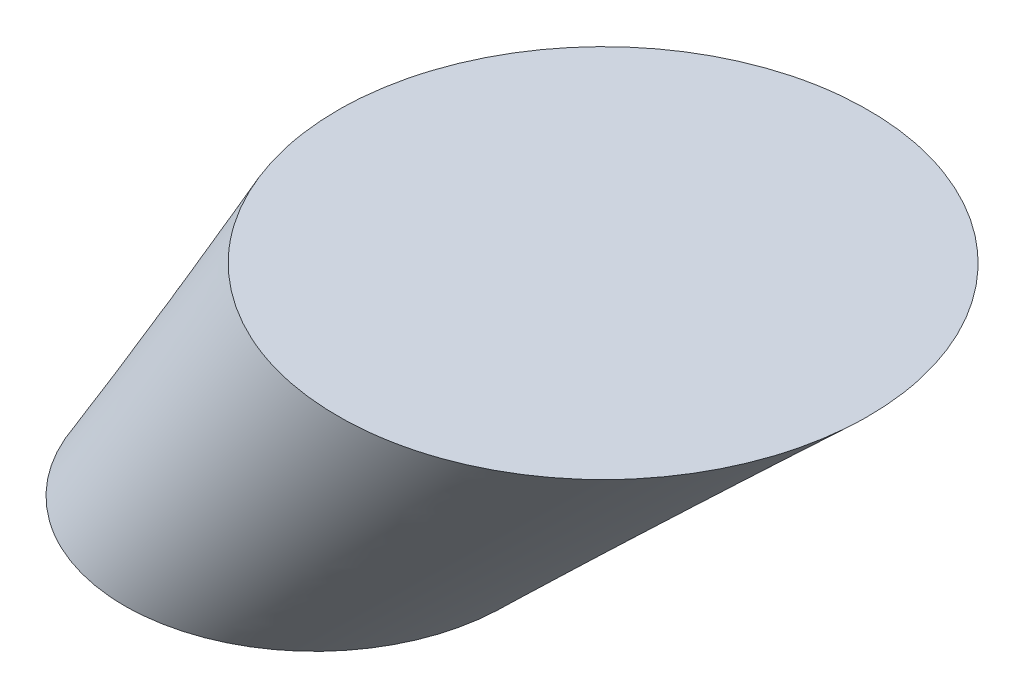
SolidWorks part; units mm, degrees
ref_plane "Front Plane" through (0, 0, 0) normal (0, 0, 1) x (1, 0, 0)
ref_plane "Top Plane" through (0, 0, 0) normal (0, 1, 0) x (1, 0, 0)
ref_plane "Right Plane" through (0, 0, 0) normal (1, 0, 0) x (0, 0, -1)
sketch "Sketch1" plane through (0, 0, 0) normal (0, 1, 0) x (1, 0, 0)
  line L0 (0, 0) -> (-47.9811, 0) construction
  circle A0 centre (0, 0) radius 23
  dimension "D1" = 46
ref_plane "Plane1" through (0, -30, 0) normal (0, -1, 0) x (-1, 0, 0)
sketch "Sketch9" plane through (0, -30, 0) normal (0, -1, 0) x (-1, 0, 0)
  circle A0 centre (25, 0) radius 16.5
  dimension "D1" = 33
  dimension "D2" = 25
loft "Loft1" add profiles "Sketch9", "Sketch1" connector at (-20.6661, -30, -15.9207) connector at (1.0526, 0, -22.9759)
sketch "Sketch13" plane through (0, 0, 0) normal (0, 1, 0) x (1, 0, 0)
  circle A0 centre (0, 0) radius 20
  dimension "D1" = 40
sketch "Sketch14" plane through (0, -30, 0) normal (0, -1, 0) x (1, 0, 0)
  circle A0 centre (-25, 0) radius 13.5
  dimension "D1" = 27
ref_plane "Plane2" through (0, -12.9, 0) normal (0, -1, 0) x (-1, 0, 0)
sketch "Sketch20" plane through (0, -12.9, 0) normal (0, -1, 0) x (-1, 0, 0)
  spline S0 degree 3 poles (9.1174, 20.0448) (7.4555, 19.8395) (6.5785, 19.6788) (4.7436, 19.1985) (3.7855, 18.8786) (1.817, 18.0307) (0.8064, 17.5024) (-1.2126, 16.1896) (-2.2211, 15.4047) (-4.1512, 13.5465) (-5.0724, 12.4726) (-6.7172, 10.0405) (-7.4398, 8.6818) (-8.5709, 5.7398) (-8.9781, 4.1568) (-9.3918, 0.8854) (-9.3974, -0.8017) (-8.9869, -4.1254) (-8.5708, -5.7604) (-7.3734, -8.8327) (-6.5932, -10.2691) (-4.7802, -12.8474) (-3.7487, -13.9894) (-1.5614, -15.9481) (-0.4066, -16.7655) (1.9177, -18.0981) (3.0868, -18.6141) (5.3646, -19.396) (6.4734, -19.6626) (8.589, -20.0059) (9.5962, -20.083) (11.4929, -20.1024) (12.3826, -20.0448) (14.0445, -19.8395) (14.9215, -19.6788) (16.7564, -19.1985) (17.7145, -18.8786) (19.683, -18.0307) (20.6936, -17.5024) (22.7126, -16.1896) (23.7211, -15.4047) (25.6512, -13.5465) (26.5724, -12.4726) (28.2172, -10.0405) (28.9398, -8.6818) (30.0709, -5.7398) (30.4781, -4.1568) (30.8918, -0.8854) (30.8974, 0.8017) (30.4869, 4.1254) (30.0708, 5.7604) (28.8734, 8.8327) (28.0932, 10.2691) (26.2802, 12.8474) (25.2487, 13.9894) (23.0614, 15.9481) (21.9066, 16.7655) (19.5823, 18.0981) (18.4132, 18.6141) (16.1354, 19.396) (15.0266, 19.6626) (12.911, 20.0059) (11.9038, 20.083) (10.0071, 20.1024) (9.1174, 20.0448) (7.4555, 19.8395) (6.5785, 19.6788) knots -0.03125 -0.03125 0 0 0.03125 0.03125 0.0625 0.0625 0.09375 0.09375 0.125 0.125 0.15625 0.15625 0.1875 0.1875 0.21875 0.21875 0.25 0.25 0.28125 0.28125 0.3125 0.3125 0.34375 0.34375 0.375 0.375 0.40625 0.40625 0.4375 0.4375 0.46875 0.46875 0.5 0.5 0.53125 0.53125 0.5625 0.5625 0.59375 0.59375 0.625 0.625 0.65625 0.65625 0.6875 0.6875 0.71875 0.71875 0.75 0.75 0.78125 0.78125 0.8125 0.8125 0.84375 0.84375 0.875 0.875 0.90625 0.90625 0.9375 0.9375 0.96875 0.96875 1 1 1.03125 1.03125 1.0625 only from (8.2865, 19.9421) to (8.2865, 19.9421)
  spline S1 degree 3 poles (9.1174, 20.0448) (7.4555, 19.8395) (6.5785, 19.6788) (4.7436, 19.1985) (3.7855, 18.8786) (1.817, 18.0307) (0.8064, 17.5024) (-1.2126, 16.1896) (-2.2211, 15.4047) (-4.1512, 13.5465) (-5.0724, 12.4726) (-6.7172, 10.0405) (-7.4398, 8.6818) (-8.5709, 5.7398) (-8.9781, 4.1568) (-9.3918, 0.8854) (-9.3974, -0.8017) (-8.9869, -4.1254) (-8.5708, -5.7604) (-7.3734, -8.8327) (-6.5932, -10.2691) (-4.7802, -12.8474) (-3.7487, -13.9894) (-1.5614, -15.9481) (-0.4066, -16.7655) (1.9177, -18.0981) (3.0868, -18.6141) (5.3646, -19.396) (6.4734, -19.6626) (8.589, -20.0059) (9.5962, -20.083) (11.4929, -20.1024) (12.3826, -20.0448) (14.0445, -19.8395) (14.9215, -19.6788) (16.7564, -19.1985) (17.7145, -18.8786) (19.683, -18.0307) (20.6936, -17.5024) (22.7126, -16.1896) (23.7211, -15.4047) (25.6512, -13.5465) (26.5724, -12.4726) (28.2172, -10.0405) (28.9398, -8.6818) (30.0709, -5.7398) (30.4781, -4.1568) (30.8918, -0.8854) (30.8974, 0.8017) (30.4869, 4.1254) (30.0708, 5.7604) (28.8734, 8.8327) (28.0932, 10.2691) (26.2802, 12.8474) (25.2487, 13.9894) (23.0614, 15.9481) (21.9066, 16.7655) (19.5823, 18.0981) (18.4132, 18.6141) (16.1354, 19.396) (15.0266, 19.6626) (12.911, 20.0059) (11.9038, 20.083) (10.0071, 20.1024) (9.1174, 20.0448) (7.4555, 19.8395) (6.5785, 19.6788) knots -0.03125 -0.03125 0 0 0.03125 0.03125 0.0625 0.0625 0.09375 0.09375 0.125 0.125 0.15625 0.15625 0.1875 0.1875 0.21875 0.21875 0.25 0.25 0.28125 0.28125 0.3125 0.3125 0.34375 0.34375 0.375 0.375 0.40625 0.40625 0.4375 0.4375 0.46875 0.46875 0.5 0.5 0.53125 0.53125 0.5625 0.5625 0.59375 0.59375 0.625 0.625 0.65625 0.65625 0.6875 0.6875 0.71875 0.71875 0.75 0.75 0.78125 0.78125 0.8125 0.8125 0.84375 0.84375 0.875 0.875 0.90625 0.90625 0.9375 0.9375 0.96875 0.96875 1 1 1.03125 1.03125 1.0625 only from (18.1381, 18.6862) to (18.1381, 18.6862)
  point P1 (18.1381, 18.6862)
ref_plane "Plane3" through (0, -9.9, 0) normal (0, -1, 0) x (-1, 0, 0)
sketch "Sketch21" plane through (0, -9.9, 0) normal (0, -1, 0) x (-1, 0, 0)
  spline S0 degree 3 poles (6.9749, 20.7366) (5.2543, 20.5587) (4.3452, 20.4107) (2.4401, 19.9522) (1.4439, 19.6415) (-0.6066, 18.8062) (-1.6612, 18.2812) (-3.7734, 16.9668) (-4.8311, 16.1767) (-6.8627, 14.2971) (-7.8362, 13.2068) (-9.5849, 10.7286) (-10.3591, 9.3401) (-11.5877, 6.3247) (-12.0408, 4.698) (-12.5352, 1.3276) (-12.5756, -0.4148) (-12.2197, -3.856) (-11.8236, -5.5533) (-10.6499, -8.7511) (-9.8735, -10.2506) (-8.0538, -12.9508) (-7.0118, -14.1514) (-4.7929, -16.2194) (-3.6169, -17.0874) (-1.2437, -18.5114) (-0.0467, -19.0683) (2.2899, -19.9226) (3.4296, -20.2207) (5.6077, -20.6187) (6.6464, -20.7189) (8.6049, -20.7779) (9.5251, -20.7366) (11.2457, -20.5587) (12.1548, -20.4107) (14.0599, -19.9522) (15.0561, -19.6415) (17.1066, -18.8062) (18.1612, -18.2812) (20.2734, -16.9668) (21.3311, -16.1767) (23.3627, -14.2971) (24.3362, -13.2068) (26.0849, -10.7286) (26.8591, -9.3401) (28.0877, -6.3247) (28.5408, -4.698) (29.0352, -1.3276) (29.0756, 0.4148) (28.7197, 3.856) (28.3236, 5.5533) (27.1499, 8.7511) (26.3735, 10.2506) (24.5538, 12.9508) (23.5118, 14.1514) (21.2929, 16.2194) (20.1169, 17.0874) (17.7437, 18.5114) (16.5467, 19.0683) (14.2101, 19.9226) (13.0704, 20.2207) (10.8923, 20.6187) (9.8536, 20.7189) (7.8951, 20.7779) (6.9749, 20.7366) (5.2543, 20.5587) (4.3452, 20.4107) knots -0.03125 -0.03125 0 0 0.03125 0.03125 0.0625 0.0625 0.09375 0.09375 0.125 0.125 0.15625 0.15625 0.1875 0.1875 0.21875 0.21875 0.25 0.25 0.28125 0.28125 0.3125 0.3125 0.34375 0.34375 0.375 0.375 0.40625 0.40625 0.4375 0.4375 0.46875 0.46875 0.5 0.5 0.53125 0.53125 0.5625 0.5625 0.59375 0.59375 0.625 0.625 0.65625 0.65625 0.6875 0.6875 0.71875 0.71875 0.75 0.75 0.78125 0.78125 0.8125 0.8125 0.84375 0.84375 0.875 0.875 0.90625 0.90625 0.9375 0.9375 0.96875 0.96875 1 1 1.03125 1.03125 1.0625 only from (6.1146, 20.6477) to (6.1146, 20.6477)
  spline S1 degree 3 poles (6.9749, 20.7366) (5.2543, 20.5587) (4.3452, 20.4107) (2.4401, 19.9522) (1.4439, 19.6415) (-0.6066, 18.8062) (-1.6612, 18.2812) (-3.7734, 16.9668) (-4.8311, 16.1767) (-6.8627, 14.2971) (-7.8362, 13.2068) (-9.5849, 10.7286) (-10.3591, 9.3401) (-11.5877, 6.3247) (-12.0408, 4.698) (-12.5352, 1.3276) (-12.5756, -0.4148) (-12.2197, -3.856) (-11.8236, -5.5533) (-10.6499, -8.7511) (-9.8735, -10.2506) (-8.0538, -12.9508) (-7.0118, -14.1514) (-4.7929, -16.2194) (-3.6169, -17.0874) (-1.2437, -18.5114) (-0.0467, -19.0683) (2.2899, -19.9226) (3.4296, -20.2207) (5.6077, -20.6187) (6.6464, -20.7189) (8.6049, -20.7779) (9.5251, -20.7366) (11.2457, -20.5587) (12.1548, -20.4107) (14.0599, -19.9522) (15.0561, -19.6415) (17.1066, -18.8062) (18.1612, -18.2812) (20.2734, -16.9668) (21.3311, -16.1767) (23.3627, -14.2971) (24.3362, -13.2068) (26.0849, -10.7286) (26.8591, -9.3401) (28.0877, -6.3247) (28.5408, -4.698) (29.0352, -1.3276) (29.0756, 0.4148) (28.7197, 3.856) (28.3236, 5.5533) (27.1499, 8.7511) (26.3735, 10.2506) (24.5538, 12.9508) (23.5118, 14.1514) (21.2929, 16.2194) (20.1169, 17.0874) (17.7437, 18.5114) (16.5467, 19.0683) (14.2101, 19.9226) (13.0704, 20.2207) (10.8923, 20.6187) (9.8536, 20.7189) (7.8951, 20.7779) (6.9749, 20.7366) (5.2543, 20.5587) (4.3452, 20.4107) knots -0.03125 -0.03125 0 0 0.03125 0.03125 0.0625 0.0625 0.09375 0.09375 0.125 0.125 0.15625 0.15625 0.1875 0.1875 0.21875 0.21875 0.25 0.25 0.28125 0.28125 0.3125 0.3125 0.34375 0.34375 0.375 0.375 0.40625 0.40625 0.4375 0.4375 0.46875 0.46875 0.5 0.5 0.53125 0.53125 0.5625 0.5625 0.59375 0.59375 0.625 0.625 0.65625 0.65625 0.6875 0.6875 0.71875 0.71875 0.75 0.75 0.78125 0.78125 0.8125 0.8125 0.84375 0.84375 0.875 0.875 0.90625 0.90625 0.9375 0.9375 0.96875 0.96875 1 1 1.03125 1.03125 1.0625 only from (6.1146, 20.6477) to (6.1146, 20.6477)
